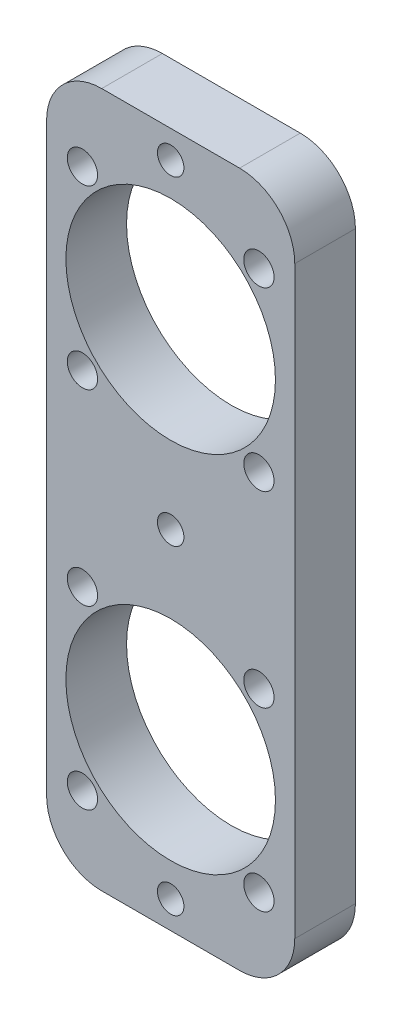
SolidWorks part; units mm, degrees
material "ABS"
ref_plane "X-Y Datum" through (0, 0, 0) normal (0, 0, 1) x (1, 0, 0)
ref_plane "X-Z Datum" through (0, 0, 0) normal (0, 1, 0) x (1, 0, 0)
ref_plane "Y-Z Datum" through (0, 0, 0) normal (1, 0, 0) x (0, 0, -1)
sketch "Sketch1" plane through (0, 0, 0) normal (0, 0, 1) x (1, 0, 0)
  line L0 (0, 30) -> (0, 20) construction
  line L1 (-22.5, 0) -> (22.5, 0) construction
  line L5 (-22.5, -30) -> (22.5, -30)
  line L6 (-22.5, -30) -> (-22.5, 30)
  line L7 (-22.5, 30) -> (22.5, 30)
  line L8 (22.5, -30) -> (22.5, 30)
  line L9 (-22.5, -30) -> (22.5, 30) construction
  line L10 (-22.5, 30) -> (22.5, -30) construction
  line L12 (-22.5, 20) -> (22.5, 20) construction
  circle A0 centre (0, 25) radius 2 construction
  circle A1 centre (0, -25) radius 2 construction
  point P2 (0, 0)
  dimension "D3" = 4
  dimension "D1" = 45
  dimension "D2" = 60
  dimension "D4" = 5
extrude "Boss-Extrude1" add sketch "Sketch1" against normal blind 11 contours L5 L8 L7 L6 A0 A1 region at (0, 0, 0)
sketch "Sketch6" plane through (0, 0, 0) normal (0, 0, 1) x (1, 0, 0)
  circle A0 centre (-16, 16) radius 2.75
  circle A1 centre (16, 16) radius 2.75
  circle A2 centre (16, -16) radius 2.75
  circle A3 centre (-16, -16) radius 2.75
  point P0 (-16, 16)
  point P1 (16, 16)
  point P3 (16, -16)
  point P5 (-16, -16)
  dimension "D1" = 5.5
extrude "Cut-Extrude2" cut sketch "Sketch6" against normal blind 8.5
sketch "Sketch7" plane through (0, 0, 0) normal (0, 0, 1) x (1, 0, 0)
  arc A0 (-19, 0) -> (19, 0) centre (0, 0) ccw construction
  arc A1 (-19, 0) -> (19, 0) centre (0, 0) ccw
  circle A2 centre (0, 0) radius 19
extrude "Cut-Extrude3" cut sketch "Sketch7" against normal through all contours A1 A2 region at (0, 0, 0)
sketch "Sketch11" plane through (0, -30, 0) normal (0, -1, 0) x (1, 0, 0)
  line L4 (-22.5, 0) -> (-22.5, -11)
  line L5 (-22.5, -11) -> (22.5, -11)
  line L6 (22.5, -11) -> (22.5, 0)
  line L7 (22.5, 0) -> (-22.5, 0)
  line L8 (-22.5, 0) -> (-22.5, -11)
  line L9 (-22.5, -11) -> (22.5, -11)
  line L10 (22.5, -11) -> (22.5, 0)
  line L11 (22.5, 0) -> (-22.5, 0)
  dimension "D1" = 0
extrude "Boss-Extrude2" add sketch "Sketch11" along normal blind 6
ref_plane "Plane1" through (0, -33, 0) normal (0, -1, 0) x (-1, 0, 0)
mirror "Mirror1" about plane through (0, -33, 0) normal (0, -1, 0) of "Cut-Extrude3", "Cut-Extrude2", "Boss-Extrude1"
sketch "Sketch12" plane through (0, 0, 0) normal (0, 0, 1) x (1, 0, 0)
  line L0 (0, -96) -> (0, -30)
  line L1 (-22.5, -96) -> (22.5, -96) construction
  line L2 (-22.5, -30) -> (22.5, -30) construction
  line L4 (-22.5, -30) -> (22.5, -30)
  line L5 (22.5, -30) -> (22.5, 30)
  line L6 (22.5, 30) -> (-22.5, 30)
  line L7 (-22.5, 30) -> (-22.5, -30)
  line L8 (-22.5, -30) -> (22.5, -30)
  line L9 (22.5, -30) -> (22.5, 30)
  line L10 (22.5, 30) -> (-22.5, 30)
  line L11 (-22.5, 30) -> (-22.5, -30)
  circle A0 centre (0, -33) radius 2
  circle A1 centre (0, -91) radius 2
  point P15 (0, -92.0624)
  dimension "D2" = 4
  dimension "D4" = 3
  dimension "D3" = 5
  dimension "D1" = 0
hole_wizard "M4 Clearance Hole2" positions "Sketch15" profile "Sketch14" hole size "M4" standard "ANSI Metric" end condition through all
sketch "Sketch15" plane through (0, 0, 0) normal (0, 0, 1) x (1, 0, 0)
  point P0 (0, -91)
  point P3 (0, -33)
  point P6 (0, 25)
sketch "Sketch14" plane through (0, -91, 0) normal (1, 0, 0) x (0, -1, 0)
  line L0 (0, 0) -> (0, 11)
  line L1 (0, 11) -> (2.4, 11)
  line L2 (2.4, 11) -> (2.4, 0)
  line L5 (2.4, 0) -> (0, 0)
  line L11 (0, -6.35) -> (0, 107.95) construction
  dimension "Thru Hole Dia." = 4.8
  dimension "Thru Hole Depth" = 11
fillet "Fillet1" radius 10 4 edges at (-22.5, -96, -5.5) (22.5, -96, -5.5) (22.5, 30, -5.5) (-22.5, 30, -5.5)
